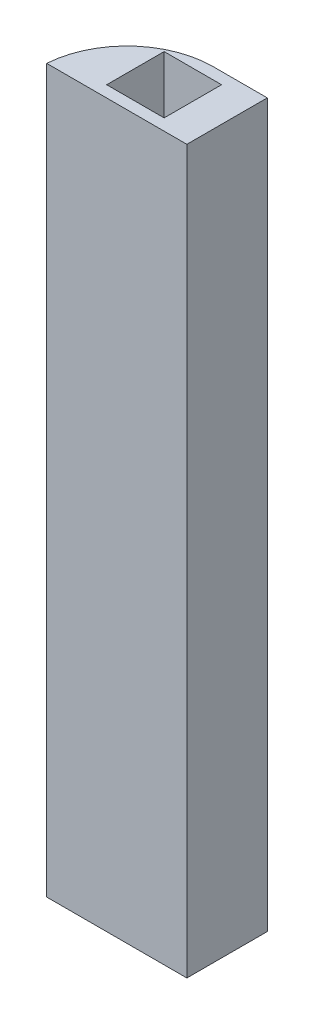
SolidWorks part; units mm, degrees
ref_plane "Спереди" through (0, 0, 0) normal (0, 0, 1) x (1, 0, 0)
ref_plane "Сверху" through (0, 0, 0) normal (0, 1, 0) x (1, 0, 0)
ref_plane "Справа" through (0, 0, 0) normal (1, 0, 0) x (0, 0, -1)
sketch "Эскиз1" plane through (0, 0, 0) normal (0, 1, 0) x (1, 0, 0)
  line L1 (-12.2, 7) -> (12.2, 7)
  line L2 (-12.2, 7) -> (-12.2, -7)
  line L3 (-12.2, -7) -> (12.2, -7)
  line L4 (12.2, 7) -> (12.2, -7)
  line L5 (-12.2, 7) -> (12.2, -7) construction
  line L6 (-12.2, -7) -> (12.2, 7) construction
  point P0 (0, 0)
extrude "Бобышка-Вытянуть1" add sketch "Эскиз1" along normal blind 125.7
sketch "Эскиз5" plane through (0, 0, 0) normal (0, -1, 0) x (-1, 0, 0)
  line L0 (-12.2, -7) -> (-1.24, -7)
  line L1 (12.2, -7) -> (-12.2, -7) construction
  line L2 (-1.24, -7) -> (-1.24, 7)
  line L3 (-12.2, 7) -> (12.2, 7) construction
  line L4 (-1.24, 7) -> (-1.2365, 5.0083)
  line L5 (-1.2365, 5.0083) -> (0, 0)
  line L6 (-1.24, 0) -> (0, 0)
  line L8 (3.76, -5) -> (-6.24, -5)
  line L9 (3.76, -5) -> (3.76, 5)
  line L10 (3.76, 5) -> (-6.24, 5)
  line L11 (-6.24, -5) -> (-6.24, 5)
  line L12 (3.76, -5) -> (-6.24, 5) construction
  line L13 (3.76, 5) -> (-6.24, -5) construction
sketch "Эскиз6" plane through (0, 0, 0) normal (0, -1, 0) x (1, 0, 0)
extrude "Вырез-Вытянуть1" cut sketch "Эскиз5" against normal blind 125.7 contours L9 L10 L5 L6 L2 L8 | L11 L8 L2 L10 | L5 L10 L2 L6 region at (3.74, 0, 0) region at (-1.3986, 0, 0.1112) region at (0.8267, 0, -1.6741)
fillet "Скругление1" radius 15 1 edges at (-12.2, 62.85, -7)
